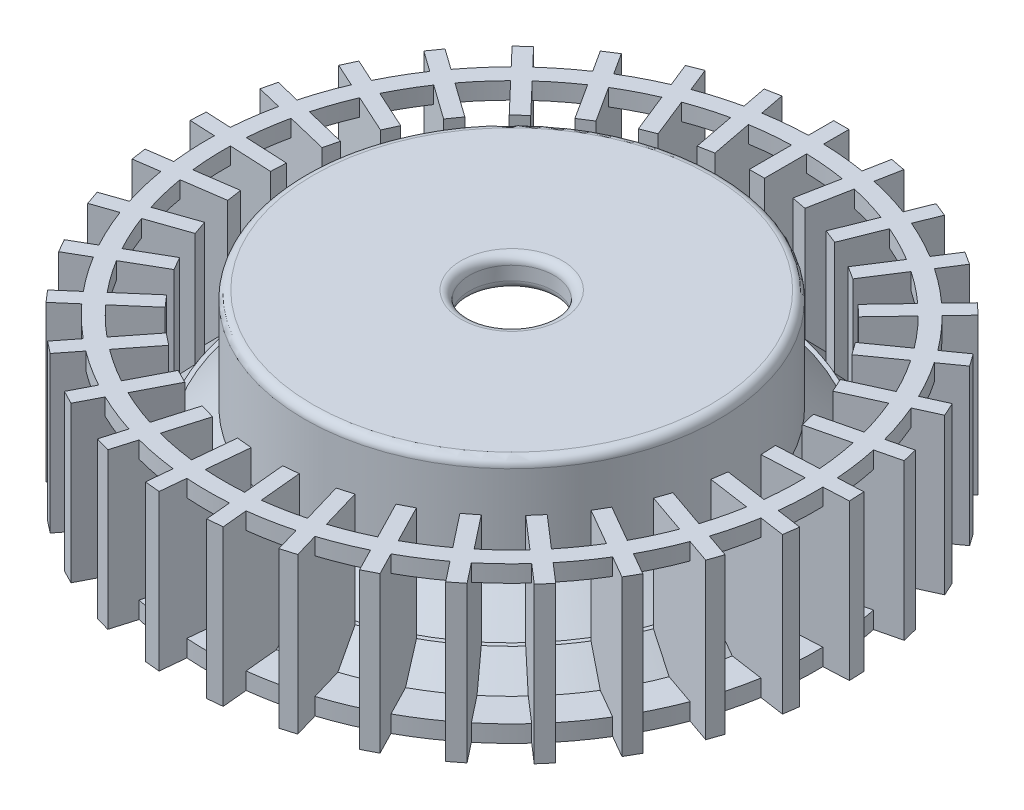
SolidWorks part; units mm, degrees
note: '?' marks a value the reader was unsure of.
material "PET"
ref_plane "Спереди" through (0, 0, 0) normal (0, 0, 1) x (1, 0, 0)
ref_plane "Сверху" through (0, 0, 0) normal (0, 1, 0) x (1, 0, 0)
ref_plane "Справа" through (0, 0, 0) normal (1, 0, 0) x (0, 0, -1)
sketch "Эскиз1" plane through (0, 0, 0) normal (0, 1, 0) x (1, 0, 0)
  circle A0 centre (0, 0) radius 18
  dimension "D1" = 36
extrude "Бобышка-Вытянуть1" add sketch "Эскиз1" along normal blind 1
sketch "Эскиз2" plane through (0, 1, 0) normal (0, 1, 0) x (1, 0, 0)
  circle A0 centre (0, 0) radius 16
  circle A1 centre (0, 0) radius 18 construction
  dimension "D1" = 2
extrude "Бобышка-Вытянуть2" add sketch "Эскиз2" along normal blind 1.5
chamfer "Фаска1" distance 1.5 angle 45 1 edges at (0, 2.5, 16)
sketch "Эскиз3" plane through (0, 2.5, 0) normal (0, 1, 0) x (1, 0, 0)
  circle A0 centre (0, 0) radius 12.25
  dimension "D1" = 24.5
extrude "Бобышка-Вытянуть3" add sketch "Эскиз3" along normal offset from surface (8 mm away) 10.5 up to face at (0, 0, 18)
fillet "Скругление1" radius 0.5 1 edges at (0, 10.5, 12.25)
sketch "Эскиз4" plane through (0, 0, 0) normal (0, 1, 0) x (1, 0, 0)
  line L0 (0, 0) -> (0, 32.8652) construction
  line L2 (-0.45, 14.5) -> (0.45, 14.5)
  line L3 (-0.45, 14.5) -> (-0.45, 19.4948)
  line L4 (-0.45, 19.4948) -> (0.45, 19.4948)
  line L5 (0.45, 14.5) -> (0.45, 19.4948)
  circle A0 centre (0, 0) radius 14.5 construction
  circle A1 centre (0, 0) radius 19.5 construction
  point P9 (0, 19.4948)
  point P11 (0, 14.5)
  dimension "D1" = 29
  dimension "D2" = 39
  dimension "D3" = 0.9
extrude "Бобышка-Вытянуть4" add sketch "Эскиз4" along normal blind 9.2
pattern_circular "Круговой массив1" count 33 over 360 about axis through (0, 0, 0) along (0, 1, 0) of "Бобышка-Вытянуть4"
sketch "Эскиз5" plane through (0, 0, 0) normal (0, -1, 0) x (1, 0, 0)
  circle A0 centre (0, 0) radius 14.6
  dimension "D1" = 29.2
extrude "Вырез-Вытянуть1" cut sketch "Эскиз5" against normal blind 1.2
chamfer "Фаска2" distance 0.7 angle 45 1 edges at (0, 0, -14.6)
sketch "Эскиз6" plane through (0, 1.2, 0) normal (0, -1, 0) x (1, 0, 0)
  circle A0 centre (0, 0) radius 11.4
  dimension "D1" = 22.8
extrude "Вырез-Вытянуть2" cut sketch "Эскиз6" against normal blind 8.5
sketch "Sketch1" plane through (0, 9.2, 0) normal (0, 1, 0) x (1, 0, 0)
  circle A0 centre (0, 0) radius 19.5
  circle A1 centre (0, 0) radius 18.5
  circle A2 centre (0, 0) radius 18
  circle A3 centre (0, 0) radius 17
  dimension "D1" = 1
  dimension "D2" = 1
extrude "Boss-Extrude1" add sketch "Sketch1" against normal blind 1
sketch "Sketch3" plane through (0, 1.2, 0) normal (0, -1, 0) x (1, 0, 0)
  circle A0 centre (0, 0) radius 11.2
  circle A1 centre (0, 0) radius 11.4
  dimension "D1" = 22.4
extrude "Boss-Extrude3" add sketch "Sketch3" against normal through all
sketch "Sketch5" plane through (0, 9.7, 0) normal (0, -1, 0) x (1, 0, 0)
  circle A0 centre (0, 0) radius 11.2 construction
  circle A1 centre (0, 0) radius 11.2
extrude "Boss-Extrude4" add sketch "Sketch5" along normal blind 1
fillet "Fillet1" radius 0.5 1 edges at (0, 8.7, -11.2)
sketch "Sketch6" plane through (0, 10.5, 0) normal (0, 1, 0) x (1, 0, 0)
  circle A0 centre (0, 0) radius 2.5
  dimension "D1" = 5
extrude "Cut-Extrude1" cut sketch "Sketch6" against normal through all
sketch "Sketch7" plane through (0, 0, 0) normal (1, 0, 0) x (0, 0, -1)
  line L0 (2.5, 10.5) -> (-2.5, 10.5) construction
  circle A0 centre (0, 6.5) radius 2
  dimension "D1" = 4
  dimension "D2" = 4
extrude "Cut-Extrude2" [suppressed] cut sketch "Sketch7" against normal up to surface and the other way up to surface
ref_axis "Axis1" through (0, 8.7, 0) along (0, 1, 0)?
pattern_circular "CirPattern1" [suppressed] count 4 every 90 about axis through (0, 8.7, 0) along (0, 1, 0)
fillet "Fillet2" [suppressed] radius 0.5
fillet "Fillet3" radius 0.5 2 edges at (0, 8.7, -2.5) (0, 10.5, 2.5)
sketch "Sketch10" plane through (0, 1.2, 0) normal (0, -1, 0) x (1, 0, 0)
  circle A1 centre (0, 0) radius 14.6
  circle A4 centre (0, 0) radius 14.6
  dimension "D1" = 0
extrude "Cut-Extrude4" cut sketch "Sketch10" against normal blind 0.5
chamfer "Chamfer1" distance 1 angle 45 1 edges at (0, 1.7, -14.6)
fillet "Fillet4" radius 0.001 33 edges at (-10.9584, 2.5, -9.4955) (-12.5574, 2.5, -7.25) (-13.7025, 2.5, -4.7425) (-14.3524, 2.5, -2.0636) (-14.4836, 2.5, 0.6899) (-14.0913, 2.5, 3.4185) (-13.1897, 2.5, 6.0235) (-11.8114, 2.5, 8.4108) (-10.0061, 2.5, 10.4941) (-7.8393, 2.5, 12.1982) (-5.3891, 2.5, 13.4613) (-2.7441, 2.5, 14.238) (0, 2.5, 14.5) (2.7441, 2.5, 14.238) (5.3891, 2.5, 13.4613) (-4.0851, 2.5, -13.9126) (7.8393, 2.5, 12.1982) (10.0061, 2.5, 10.4941) (11.8114, 2.5, 8.4108) (13.1897, 2.5, 6.0235) (14.0913, 2.5, 3.4185) (14.4836, 2.5, 0.6899) (14.3524, 2.5, -2.0636) (13.7025, 2.5, -4.7425) (12.5574, 2.5, -7.25) (10.9584, 2.5, -9.4955) (-6.6443, 2.5, -12.8881) (8.9633, 2.5, -11.3978) (6.6443, 2.5, -12.8881) (4.0851, 2.5, -13.9126) (1.3783, 2.5, -14.4343) (-8.9633, 2.5, -11.3978) (-1.3783, 2.5, -14.4343)
sketch "Sketch15" plane through (0, 2.5, 0) normal (0, 1, 0) x (1, 0, 0)
  circle A0 centre (0, 0) radius 14.4953
  arc A1 (-10.898, -9.5651) -> (-9.0358, -11.3408) centre (0, 0) ccw construction
  circle A3 centre (0, 0) radius 12.25 construction
  circle A4 centre (0, 0) radius 12.25
  dimension "D1" = 0.005
extrude "Boss-Extrude6" add sketch "Sketch15" along normal blind 0.5
chamfer "Chamfer3" distance 1.5 angle 45 1 edges at (0, 3, 12.25)
chamfer "Chamfer4" distance 2.4 angle 45 1 edges at (0, 1.7, -11.2)
sketch "Sketch16" plane through (0, 0, 0) normal (0, 0, 1) x (1, 0, 0)
  line L0 (13.75, 3) -> (14.25, 2.5)
  line L1 (13.75, 3) -> (-13.75, 3) construction
  line L2 (14.4953, 3) -> (-14.4953, 3) construction
  line L3 (14.4953, 2.5) -> (-14.4953, 2.5) construction
  line L4 (14.25, 2.5) -> (14.4953, 2.5)
  line L5 (14.4953, 2.5) -> (14.4953, 3)
  line L6 (14.4953, 3) -> (13.75, 3)
revolve "Cut-Revolve1" cut sketch "Sketch16" angle 360 about axis through (0, 8.7, 0) along (0, 1, 0)
